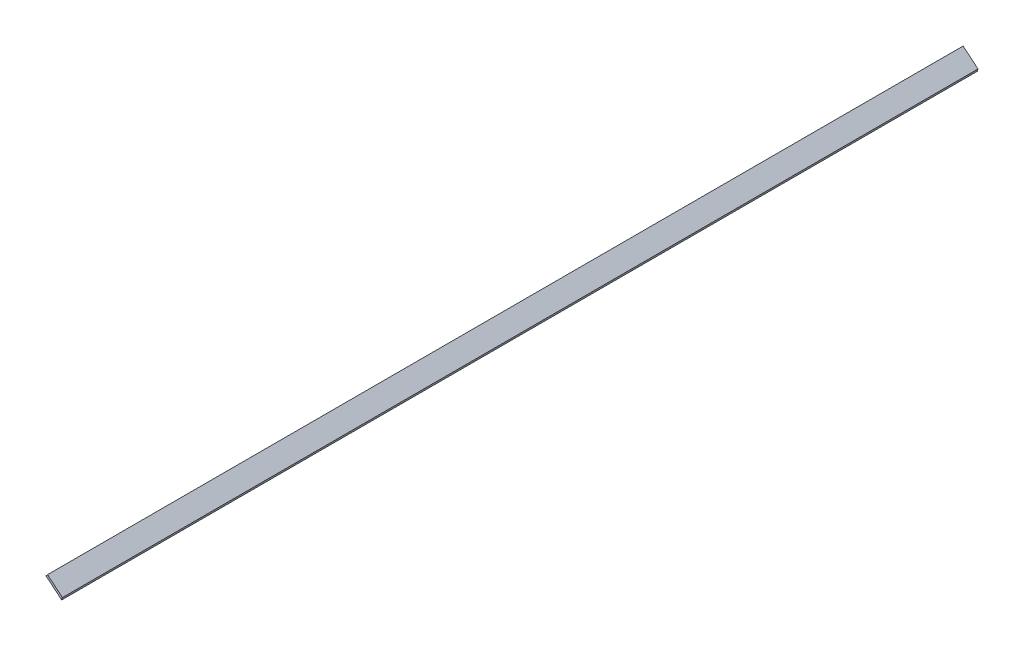
SolidWorks part; units mm, degrees
ref_plane "Front Plane" through (0, 0, 0) normal (0, 0, 1) x (1, 0, 0)
ref_plane "Top Plane" through (0, 0, 0) normal (0, 1, 0) x (1, 0, 0)
ref_plane "Right Plane" through (0, 0, 0) normal (1, 0, 0) x (0, 0, -1)
sketch "Sketch1" plane through (0, 0, 0) normal (0, 0, 1) x (1, 0, 0)
  line L0 (0, 0) -> (0.7605, 2.4411)
  line L1 (0.7605, 2.4411) -> (-13.9033, 14.6602)
  line L2 (-13.9033, 14.6602) -> (-15.4155, 12.8455)
  line L3 (-15.4155, 12.8455) -> (0, 0)
  dimension "D1" = 2.3622
  dimension "D2" = 90
  dimension "D3" = 67.5
  dimension "D4" = 20.066
extrude "Boss-Extrude1" add sketch "Sketch1" along normal blind 901.7
